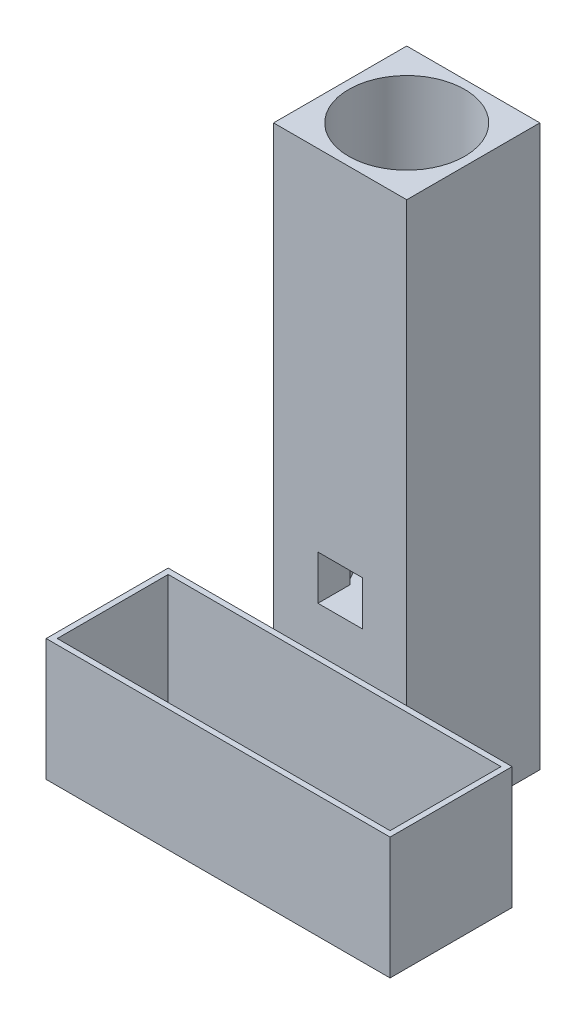
SolidWorks part; units mm, degrees
ref_plane "Front Plane" through (0, 0, 0) normal (0, 0, 1) x (1, 0, 0)
ref_plane "Top Plane" through (0, 0, 0) normal (0, 1, 0) x (1, 0, 0)
ref_plane "Right Plane" through (0, 0, 0) normal (1, 0, 0) x (0, 0, -1)
sketch "Sketch2" plane through (0, 0, 0) normal (0, 1, 0) x (1, 0, 0)
  line L0 (-7.1, 17.2376) -> (7.1, 17.2376)
  line L1 (11.3782, 14.7676) -> (18.4782, 2.47)
  line L2 (18.4782, -2.47) -> (11.3782, -14.7676)
  line L3 (7.1, -17.2376) -> (-7.1, -17.2376)
  line L4 (-11.3782, -14.7676) -> (-18.4782, -2.47)
  line L5 (-18.4782, 2.47) -> (-11.3782, 14.7676)
  line L6 (-7.1, 17.2376) -> (-11.3782, 14.7676)
  line L7 (11.3782, 14.7676) -> (7.1, 17.2376)
  line L8 (18.4782, -2.47) -> (18.4782, 2.47)
  line L9 (7.1, -17.2376) -> (11.3782, -14.7676)
  line L10 (-11.3782, -14.7676) -> (-7.1, -17.2376)
  line L11 (-18.4782, 2.47) -> (-18.4782, -2.47)
  line L13 (-30, -30) -> (30, -30)
  line L14 (-30, -30) -> (-30, 30)
  line L15 (-30, 30) -> (30, 30)
  line L16 (30, -30) -> (30, 30)
  line L17 (-30, -30) -> (30, 30) construction
  line L18 (-30, 30) -> (30, -30) construction
  circle A0 centre (0, 0) radius 28.6425
  circle A1 centre (0, 0) radius 18.6425 construction
  circle A2 centre (0, 0) radius 26.1425
  point P5 (0, 17.2376)
  point P16 (0, 0)
  dimension "D5" = 10
  dimension "D6" = 2.5
  dimension "D7" = 60
  dimension "D1" = 14.2
  dimension "D2" = 4.94
  dimension "D3" = 6
  dimension "D8" = 60
  dimension "D4" = 6
extrude "Boss-Extrude1" add sketch "Sketch2" along normal blind 50 contours A0 A2 | A2 L11 L5 L6 L0 L7 L1 L8 L2 L9 L3 L10 L4 region at (-27.8324, 0, 0) region at (-25.4031, 0, 0)
extrude "Boss-Extrude2" add sketch "Sketch2<3>" along normal blind 127.5 from surface contours A0 A2 region at (-27.8324, 0, 0) starting at face at (0, 50, 28.6425)
sketch "Sketch2<3>" plane through (0, 0, 0) normal (0, 1, 0) x (1, 0, 0) same geometry as "Sketch2"
extrude "Boss-Extrude3" add sketch "Sketch2<4>" along normal up to surface (177.5 mm away) contours A0 L15 L14 | A0 L16 L15 | A0 L13 L16 | A0 L14 L13 region at (-29.1515, 0, 0) up to face at (0, 177.5, 28.6425)
sketch "Sketch2<4>" plane through (0, 0, 0) normal (0, 1, 0) x (1, 0, 0) same geometry as "Sketch2"
sketch "Sketch3" plane through (0, 0, 0) normal (0, -1, 0) x (1, 0, 0)
  line L1 (-30, 30) -> (30, 30)
  line L2 (-30, 30) -> (-30, -30)
  line L3 (-30, -30) -> (30, -30)
  line L4 (30, 30) -> (30, -30)
extrude "Boss-Extrude4" add sketch "Sketch3" along normal blind 75
ref_plane "Plane1" through (0, -75, 0) normal (0, -1, 0) x (-1, 0, 0)
sketch "Sketch4" plane through (0, -75, 0) normal (0, -1, 0) x (-1, 0, 0)
  line L0 (-30, -30) -> (30, -30) construction
  line L1 (77.5, -30) -> (-77.5, -30)
  line L2 (77.5, -30) -> (77.5, -85)
  line L3 (77.5, -85) -> (-77.5, -85)
  line L4 (-77.5, -30) -> (-77.5, -85)
  line L6 (75, -32.5) -> (-75, -32.5)
  line L7 (75, -32.5) -> (75, -82.5)
  line L8 (75, -82.5) -> (-75, -82.5)
  line L9 (-75, -32.5) -> (-75, -82.5)
  point P5 (0, -30)
  point P13 (0, -32.5)
  dimension "D1" = 155
  dimension "D2" = 55
  dimension "D3" = 2.5
  dimension "D4" = 150
  dimension "D5" = 50
extrude "Boss-Extrude5" add sketch "Sketch4" against normal blind 5 separate body contours L7 L6 L9 L8
extrude "Boss-Extrude6" add sketch "Sketch4<4>" against normal blind 55
sketch "Sketch4<4>" plane through (0, -75, 0) normal (0, -1, 0) x (-1, 0, 0) same geometry as "Sketch4"
sketch "Sketch5" plane through (0, -75, 0) normal (0, -1, 0) x (1, 0, 0)
  circle A0 centre (0, 0) radius 20
  dimension "D1" = 40
extrude "Cut-Extrude4" cut sketch "Sketch5" against normal blind 50
sketch "Sketch6" plane through (0, 0, 30) normal (0, 0, 1) x (1, 0, 0)
  line L0 (63.25, 0) -> (-63.25, 0) construction
  line L1 (10, 20) -> (-10, 20)
  line L2 (10, 20) -> (10, 0)
  line L3 (10, 0) -> (-10, 0)
  line L4 (-10, 20) -> (-10, 0)
  line L5 (-30, 177.5) -> (-30, -20) construction
  dimension "D1" = 20
  dimension "D2" = 20
  dimension "D3" = 20
extrude "Cut-Extrude5" cut sketch "Sketch6" against normal blind 20
